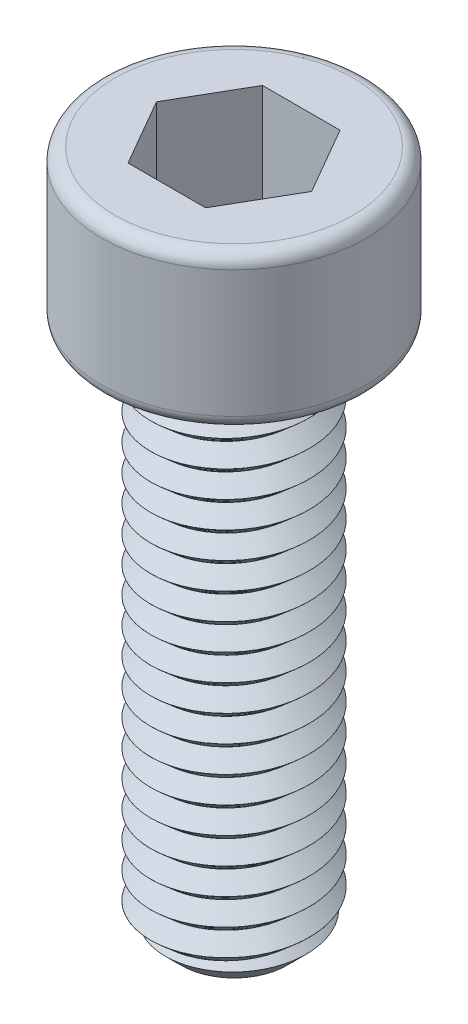
SolidWorks part; units mm, degrees
material "Plain Carbon Steel"
ref_plane "Front Plane" through (0, 0, 0) normal (0, 0, 1) x (1, 0, 0)
ref_plane "Top Plane" through (0, 0, 0) normal (0, 1, 0) x (1, 0, 0)
ref_plane "Right Plane" through (0, 0, 0) normal (1, 0, 0) x (0, 0, -1)
sketch "Sketch1" plane through (0, 0, 0) normal (0, 1, 0) x (1, 0, 0)
  circle A0 centre (0, 0) radius 3
  dimension "D1" = 6
extrude "Boss-Extrude1" add sketch "Sketch1" along normal blind 20
sketch "Sketch2" plane through (0, 20, 0) normal (0, 1, 0) x (1, 0, 0)
  circle A0 centre (0, 0) radius 5
  dimension "D1" = 10
extrude "Boss-Extrude2" add sketch "Sketch2" along normal blind 5.8
sketch "Sketch3" plane through (0, 25.8, 0) normal (0, 1, 0) x (1, 0, 0)
  line L1 (2.9329, 0) -> (1.4665, 2.54)
  line L2 (1.4665, 2.54) -> (-1.4665, 2.54)
  line L3 (-1.4665, 2.54) -> (-2.9329, 0)
  line L4 (-2.9329, 0) -> (-1.4665, -2.54)
  line L5 (-1.4665, -2.54) -> (1.4665, -2.54)
  line L6 (1.4665, -2.54) -> (2.9329, 0)
  circle A0 centre (0, 0) radius 2.54 construction
  dimension "D1" = 5.08
extrude "Cut-Extrude1" cut sketch "Sketch3" against normal blind 4.2
fillet "Fillet3" radius 0.5 2 edges at (0, 20, 5) (0, 25.8, 5)
sketch "Sketch4" plane through (0, 0, 0) normal (0, 0, 1) x (1, 0, 0)
  line L0 (2.43, 0) -> (3, 0.499)
  line L1 (-3, 0) -> (3, 0) construction
  line L2 (2.43, 0) -> (3, -0.499)
  line L3 (3, -0.499) -> (3, 0)
  line L4 (3, 0) -> (3, 20) construction
  line L5 (3, 0.499) -> (3, 0)
  dimension "D1" = 0.499
  dimension "D2" = 0.499
  dimension "D3" = 0.57
sketch "Sketch5" plane through (0, 0, 0) normal (0, 1, 0) x (1, 0, 0)
  circle A0 centre (0, 0) radius 3
curve "Helix/Spiral1" pitch 1 height 19 radius 3 centre (0, 0, 0) axis (0, 1, 0) start towards (1, 0, 0)
chamfer "Chamfer1" distance 1 angle 45 1 edges at (0, 0, 3)
sweep "Cut-Sweep1" cut profiles "Sketch4" path "Helix/Spiral1"
